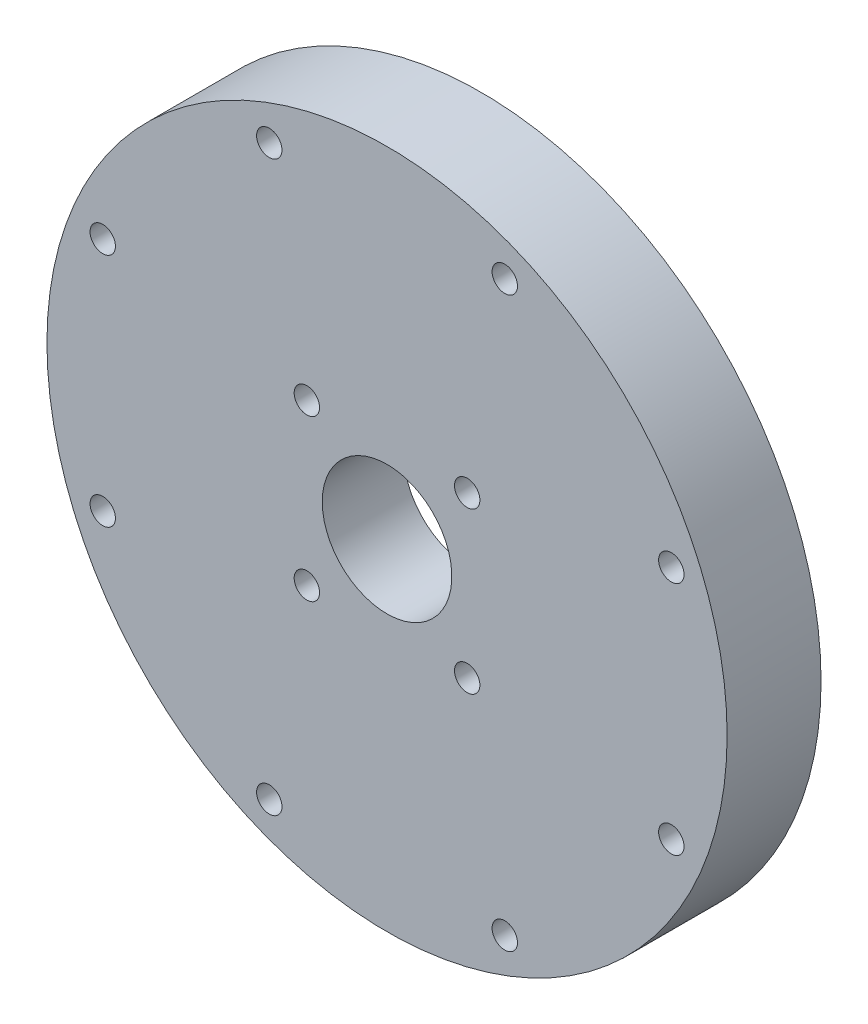
SolidWorks part; units mm, degrees
material "6061-T6 (SS)"
ref_plane "Front Plane" through (0, 0, 0) normal (0, 0, 1) x (1, 0, 0)
ref_plane "Top Plane" through (0, 0, 0) normal (0, 1, 0) x (1, 0, 0)
ref_plane "Right Plane" through (0, 0, 0) normal (1, 0, 0) x (0, 0, -1)
curve "Volute Curve"
  spline degree 3 poles (34.2618, 0, 0) (34.2648, 0.0718, 0) (34.2707, 0.2156, 0) (34.2778, 0.4312, 0) (34.2837, 0.647, 0) (34.2882, 0.8628, 0) (34.2914, 1.0787, 0) (34.2932, 1.2947, 0) (34.2937, 1.5108, 0) (34.2929, 1.7269, 0) (34.2907, 1.9431, 0) (34.2871, 2.1593, 0) (34.2822, 2.3756, 0) (34.2759, 2.5919, 0) (34.2683, 2.8082, 0) (34.2593, 3.0245, 0) (34.2489, 3.2407, 0) (34.2372, 3.457, 0) (34.2242, 3.6733, 0) (34.2098, 3.8895, 0) (34.194, 4.1058, 0) (34.1768, 4.3219, 0) (34.1583, 4.538, 0) (34.1385, 4.7541, 0) (34.1173, 4.9701, 0) (34.0947, 5.186, 0) (34.0708, 5.4018, 0) (34.0454, 5.6175, 0) (34.0188, 5.8331, 0) (33.9908, 6.0486, 0) (33.9614, 6.264, 0) (33.9306, 6.4793, 0) (33.8985, 6.6944, 0) (33.8651, 6.9094, 0) (33.8303, 7.1242, 0) (33.7941, 7.3388, 0) (33.7566, 7.5533, 0) (33.7177, 7.7676, 0) (33.6774, 7.9817, 0) (33.6358, 8.1956, 0) (33.5929, 8.4093, 0) (33.5486, 8.6228, 0) (33.5029, 8.8361, 0) (33.4559, 9.0491, 0) (33.4076, 9.2619, 0) (33.3579, 9.4745, 0) (33.3068, 9.6868, 0) (33.2544, 9.8988, 0) (33.2006, 10.1105, 0) (33.1456, 10.322, 0) (33.0891, 10.5332, 0) (33.0313, 10.744, 0) (32.9722, 10.9546, 0) (32.9118, 11.1648, 0) (32.85, 11.3748, 0) (32.7869, 11.5843, 0) (32.7224, 11.7936, 0) (32.6566, 12.0025, 0) (32.5895, 12.211, 0) (32.521, 12.4192, 0) (32.4513, 12.627, 0) (32.3802, 12.8344, 0) (32.3077, 13.0414, 0) (32.234, 13.248, 0) (32.1589, 13.4542, 0) (32.0826, 13.6599, 0) (32.0049, 13.8653, 0) (31.9259, 14.0702, 0) (31.8456, 14.2747, 0) (31.764, 14.4787, 0) (31.6811, 14.6823, 0) (31.5968, 14.8854, 0) (31.5113, 15.088, 0) (31.4245, 15.2901, 0) (31.3364, 15.4917, 0) (31.247, 15.6929, 0) (31.1563, 15.8935, 0) (31.0644, 16.0936, 0) (30.9711, 16.2932, 0) (30.8766, 16.4922, 0) (30.7808, 16.6907, 0) (30.6837, 16.8886, 0) (30.5854, 17.086, 0) (30.4858, 17.2829, 0) (30.3849, 17.4791, 0) (30.2828, 17.6748, 0) (30.1794, 17.8698, 0) (30.0747, 18.0643, 0) (29.9688, 18.2582, 0) (29.8617, 18.4514, 0) (29.7533, 18.644, 0) (29.6437, 18.836, 0) (29.5328, 19.0274, 0) (29.4208, 19.2181, 0) (29.3074, 19.4081, 0) (29.1929, 19.5975, 0) (29.0771, 19.7862, 0) (28.9601, 19.9742, 0) (28.842, 20.1616, 0) (28.7226, 20.3482, 0) (28.602, 20.5342, 0) (28.4801, 20.7194, 0) (28.3571, 20.904, 0) (28.233, 21.0877, 0) (28.1076, 21.2708, 0) (27.981, 21.4531, 0) (27.8533, 21.6347, 0) (27.7243, 21.8155, 0) (27.5942, 21.9956, 0) (27.463, 22.1748, 0) (27.3306, 22.3533, 0) (27.197, 22.531, 0) (27.0623, 22.708, 0) (26.9264, 22.8841, 0) (26.7894, 23.0594, 0) (26.6512, 23.2339, 0) (26.5119, 23.4075, 0) (26.3715, 23.5804, 0) (26.23, 23.7524, 0) (26.0873, 23.9235, 0) (25.9435, 24.0938, 0) (25.7987, 24.2632, 0) (25.6527, 24.4318, 0) (25.5056, 24.5995, 0) (25.3574, 24.7663, 0) (25.2082, 24.9322, 0) (25.0578, 25.0973, 0) (24.9064, 25.2614, 0) (24.7539, 25.4246, 0) (24.6003, 25.5869, 0) (24.4457, 25.7483, 0) (24.29, 25.9087, 0) (24.1333, 26.0682, 0) (23.9755, 26.2268, 0) (23.8167, 26.3844, 0) (23.6569, 26.541, 0) (23.496, 26.6967, 0) (23.3341, 26.8514, 0) (23.1712, 27.0051, 0) (23.0073, 27.1579, 0) (22.8424, 27.3096, 0) (22.6765, 27.4604, 0) (22.5096, 27.6101, 0) (22.3417, 27.7589, 0) (22.1728, 27.9066, 0) (22.003, 28.0533, 0) (21.8322, 28.199, 0) (21.6604, 28.3436, 0) (21.4877, 28.4872, 0) (21.314, 28.6297, 0) (21.1394, 28.7712, 0) (20.9639, 28.9116, 0) (20.7874, 29.051, 0) (20.61, 29.1892, 0) (20.4317, 29.3264, 0) (20.2524, 29.4626, 0) (20.0723, 29.5976, 0) (19.8913, 29.7315, 0) (19.7094, 29.8643, 0) (19.5266, 29.996, 0) (19.3429, 30.1266, 0) (19.1584, 30.2561, 0) (18.973, 30.3844, 0) (18.7867, 30.5116, 0) (18.5996, 30.6377, 0) (18.4117, 30.7626, 0) (18.2229, 30.8864, 0) (18.0333, 31.009, 0) (17.8429, 31.1304, 0) (17.6516, 31.2507, 0) (17.4596, 31.3698, 0) (17.2667, 31.4878, 0) (17.0731, 31.6045, 0) (16.8786, 31.7201, 0) (16.6834, 31.8344, 0) (16.4875, 31.9476, 0) (16.2907, 32.0596, 0) (16.0932, 32.1703, 0) (15.895, 32.2799, 0) (15.696, 32.3882, 0) (15.4963, 32.4953, 0) (15.2959, 32.6012, 0) (15.0947, 32.7058, 0) (14.8929, 32.8092, 0) (14.6903, 32.9114, 0) (14.487, 33.0123, 0) (14.2831, 33.1119, 0) (14.0784, 33.2103, 0) (13.8731, 33.3075, 0) (13.6672, 33.4033, 0) (13.4606, 33.4979, 0) (13.2533, 33.5912, 0) (13.0454, 33.6833, 0) (12.8368, 33.774, 0) (12.6277, 33.8635, 0) (12.4179, 33.9517, 0) (12.2075, 34.0385, 0) (11.9965, 34.1241, 0) (11.7849, 34.2084, 0) (11.5727, 34.2913, 0) (11.36, 34.373, 0) (11.1467, 34.4533, 0) (10.9328, 34.5323, 0) (10.7183, 34.61, 0) (10.5034, 34.6863, 0) (10.2879, 34.7613, 0) (10.0718, 34.835, 0) (9.8553, 34.9074, 0) (9.6382, 34.9783, 0) (9.4206, 35.048, 0) (9.2025, 35.1163, 0) (8.984, 35.1832, 0) (8.765, 35.2488, 0) (8.5455, 35.313, 0) (8.3255, 35.3759, 0) (8.1051, 35.4374, 0) (7.8842, 35.4975, 0) (7.6629, 35.5562, 0) (7.4412, 35.6136, 0) (7.2191, 35.6696, 0) (6.9965, 35.7242, 0) (6.7736, 35.7774, 0) (6.5503, 35.8292, 0) (6.3265, 35.8796, 0) (6.1024, 35.9287, 0) (5.878, 35.9763, 0) (5.6532, 36.0225, 0) (5.428, 36.0674, 0) (5.2025, 36.1108, 0) (4.9766, 36.1528, 0) (4.7505, 36.1934, 0) (4.524, 36.2326, 0) (4.2972, 36.2704, 0) (4.0701, 36.3067, 0) (3.8428, 36.3417, 0) (3.6151, 36.3752, 0) (3.3872, 36.4073, 0) (3.159, 36.438, 0) (2.9306, 36.4672, 0) (2.7019, 36.495, 0) (2.473, 36.5214, 0) (2.2439, 36.5463, 0) (2.0146, 36.5699, 0) (1.785, 36.5919, 0) (1.5553, 36.6126, 0) (1.3253, 36.6318, 0) (1.0952, 36.6495, 0) (0.8649, 36.6658, 0) (0.6345, 36.6807, 0) (0.4039, 36.6941, 0) (0.1731, 36.706, 0) (-0.0577, 36.7166, 0) (-0.2887, 36.7256, 0) (-0.5199, 36.7332, 0) (-0.7511, 36.7394, 0) (-0.9824, 36.7441, 0) (-1.2138, 36.7474, 0) (-1.4453, 36.7492, 0) (-1.6769, 36.7495, 0) (-1.9085, 36.7484, 0) (-2.1402, 36.7458, 0) (-2.3719, 36.7418, 0) (-2.6037, 36.7363, 0) (-2.8355, 36.7293, 0) (-3.0673, 36.7209, 0) (-3.2991, 36.711, 0) (-3.5309, 36.6997, 0) (-3.7627, 36.6869, 0) (-3.9944, 36.6726, 0) (-4.2262, 36.6569, 0) (-4.4579, 36.6397, 0) (-4.6895, 36.6211, 0) (-4.9211, 36.6009, 0) (-5.1526, 36.5794, 0) (-5.3841, 36.5563, 0) (-5.6154, 36.5318, 0) (-5.8467, 36.5059, 0) (-6.0779, 36.4784, 0) (-6.3089, 36.4495, 0) (-6.5399, 36.4192, 0) (-6.7706, 36.3874, 0) (-7.0013, 36.3541, 0) (-7.2318, 36.3194, 0) (-7.4621, 36.2832, 0) (-7.6923, 36.2455, 0) (-7.9223, 36.2064, 0) (-8.1521, 36.1658, 0) (-8.3817, 36.1238, 0) (-8.6111, 36.0803, 0) (-8.8403, 36.0354, 0) (-9.0693, 35.989, 0) (-9.298, 35.9411, 0) (-9.5265, 35.8918, 0) (-9.7548, 35.8411, 0) (-9.9827, 35.7889, 0) (-10.2105, 35.7352, 0) (-10.4379, 35.6802, 0) (-10.665, 35.6236, 0) (-10.8919, 35.5656, 0) (-11.1184, 35.5062, 0) (-11.3446, 35.4453, 0) (-11.5705, 35.383, 0) (-11.7961, 35.3193, 0) (-12.0213, 35.2541, 0) (-12.2461, 35.1875, 0) (-12.4706, 35.1194, 0) (-12.6948, 35.0499, 0) (-12.9185, 34.979, 0) (-13.1419, 34.9067, 0) (-13.3648, 34.8329, 0) (-13.5874, 34.7578, 0) (-13.8095, 34.6812, 0) (-14.0312, 34.6031, 0) (-14.2525, 34.5237, 0) (-14.4734, 34.4429, 0) (-14.6937, 34.3606, 0) (-14.9137, 34.2769, 0) (-15.1331, 34.1918, 0) (-15.3521, 34.1054, 0) (-15.5706, 34.0175, 0) (-15.7885, 33.9282, 0) (-16.006, 33.8375, 0) (-16.223, 33.7455, 0) (-16.4394, 33.652, 0) (-16.6553, 33.5572, 0) (-16.8707, 33.461, 0) (-17.0855, 33.3634, 0) (-17.2997, 33.2644, 0) (-17.5134, 33.164, 0) (-17.7265, 33.0623, 0) (-17.939, 32.9592, 0) (-18.151, 32.8548, 0) (-18.3623, 32.7489, 0) (-18.573, 32.6418, 0) (-18.7831, 32.5332, 0) (-18.9925, 32.4234, 0) (-19.2014, 32.3121, 0) (-19.4095, 32.1996, 0) (-19.6171, 32.0857, 0) (-19.8239, 31.9704, 0) (-20.0301, 31.8538, 0) (-20.2356, 31.7359, 0) (-20.4404, 31.6167, 0) (-20.6445, 31.4962, 0) (-20.8479, 31.3743, 0) (-21.0506, 31.2511, 0) (-21.2526, 31.1267, 0) (-21.4538, 31.0009, 0) (-21.6543, 30.8738, 0) (-21.854, 30.7454, 0) (-22.053, 30.6158, 0) (-22.2512, 30.4848, 0) (-22.4487, 30.3526, 0) (-22.6453, 30.2191, 0) (-22.8412, 30.0843, 0) (-23.0363, 29.9482, 0) (-23.2305, 29.8109, 0) (-23.424, 29.6723, 0) (-23.6166, 29.5325, 0) (-23.8084, 29.3915, 0) (-23.9994, 29.2491, 0) (-24.1895, 29.1056, 0) (-24.3787, 28.9608, 0) (-24.5671, 28.8148, 0) (-24.7546, 28.6676, 0) (-24.9413, 28.5191, 0) (-25.127, 28.3694, 0) (-25.3119, 28.2186, 0) (-25.4958, 28.0665, 0) (-25.6789, 27.9132, 0) (-25.861, 27.7587, 0) (-26.0422, 27.6031, 0) (-26.2224, 27.4463, 0) (-26.4018, 27.2882, 0) (-26.5801, 27.1291, 0) (-26.7576, 26.9687, 0) (-26.934, 26.8072, 0) (-27.1095, 26.6446, 0) (-27.284, 26.4808, 0) (-27.4575, 26.3159, 0) (-27.63, 26.1498, 0) (-27.8015, 25.9826, 0) (-27.972, 25.8143, 0) (-28.1415, 25.6448, 0) (-28.31, 25.4743, 0) (-28.4774, 25.3027, 0) (-28.6438, 25.1299, 0) (-28.8092, 24.9561, 0) (-28.9735, 24.7811, 0) (-29.1367, 24.6051, 0) (-29.2989, 24.4281, 0) (-29.46, 24.2499, 0) (-29.62, 24.0707, 0) (-29.7789, 23.8905, 0) (-29.9368, 23.7092, 0) (-30.0935, 23.5268, 0) (-30.2491, 23.3435, 0) (-30.4036, 23.1591, 0) (-30.557, 22.9737, 0) (-30.7093, 22.7872, 0) (-30.8604, 22.5998, 0) (-31.0104, 22.4114, 0) (-31.1592, 22.2219, 0) (-31.3069, 22.0315, 0) (-31.4534, 21.8402, 0) (-31.5988, 21.6478, 0) (-31.7429, 21.4545, 0) (-31.8859, 21.2602, 0) (-32.0277, 21.065, 0) (-32.1684, 20.8688, 0) (-32.3078, 20.6717, 0) (-32.446, 20.4737, 0) (-32.583, 20.2747, 0) (-32.7188, 20.0748, 0) (-32.8533, 19.8741, 0) (-32.9866, 19.6724, 0) (-33.1187, 19.4698, 0) (-33.2496, 19.2664, 0) (-33.3792, 19.0621, 0) (-33.5075, 18.8569, 0) (-33.6346, 18.6509, 0) (-33.7604, 18.444, 0) (-33.885, 18.2362, 0) (-34.0082, 18.0276, 0) (-34.1302, 17.8182, 0) (-34.2509, 17.608, 0) (-34.3703, 17.397, 0) (-34.4884, 17.1851, 0) (-34.6052, 16.9725, 0) (-34.7207, 16.7591, 0) (-34.8349, 16.5449, 0) (-34.9478, 16.3299, 0) (-35.0593, 16.1141, 0) (-35.1695, 15.8976, 0) (-35.2784, 15.6804, 0) (-35.3859, 15.4624, 0) (-35.4921, 15.2436, 0) (-35.597, 15.0242, 0) (-35.7004, 14.804, 0) (-35.8026, 14.5832, 0) (-35.9033, 14.3616, 0) (-36.0027, 14.1393, 0) (-36.1007, 13.9164, 0) (-36.1973, 13.6928, 0) (-36.2926, 13.4685, 0) (-36.3864, 13.2436, 0) (-36.4789, 13.018, 0) (-36.57, 12.7918, 0) (-36.6596, 12.5649, 0) (-36.7479, 12.3374, 0) (-36.8348, 12.1094, 0) (-36.9202, 11.8807, 0) (-37.0042, 11.6514, 0) (-37.0868, 11.4215, 0) (-37.168, 11.1911, 0) (-37.2477, 10.96, 0) (-37.326, 10.7285, 0) (-37.4029, 10.4963, 0) (-37.4783, 10.2637, 0) (-37.5523, 10.0305, 0) (-37.6248, 9.7967, 0) (-37.6959, 9.5625, 0) (-37.7655, 9.3277, 0) (-37.8337, 9.0925, 0) (-37.9004, 8.8568, 0) (-37.9656, 8.6205, 0) (-38.0293, 8.3839, 0) (-38.0916, 8.1467, 0) (-38.1524, 7.9091, 0) (-38.2117, 7.6711, 0) (-38.2696, 7.4326, 0) (-38.3259, 7.1937, 0) (-38.3808, 6.9544, 0) (-38.4342, 6.7147, 0) (-38.486, 6.4746, 0) (-38.5364, 6.2341, 0) (-38.5853, 5.9932, 0) (-38.6326, 5.7519, 0) (-38.6785, 5.5103, 0) (-38.7229, 5.2684, 0) (-38.7657, 5.0261, 0) (-38.807, 4.7835, 0) (-38.8468, 4.5405, 0) (-38.8851, 4.2973, 0) (-38.9219, 4.0537, 0) (-38.9571, 3.8099, 0) (-38.9908, 3.5657, 0) (-39.023, 3.3213, 0) (-39.0537, 3.0767, 0) (-39.0828, 2.8317, 0) (-39.1104, 2.5866, 0) (-39.1364, 2.3412, 0) (-39.1609, 2.0955, 0) (-39.1839, 1.8497, 0) (-39.2053, 1.6037, 0) (-39.2252, 1.3574, 0) (-39.2435, 1.111, 0) (-39.2603, 0.8644, 0) (-39.2756, 0.6176, 0) (-39.2893, 0.3707, 0) (-39.3014, 0.1236, 0) (-39.312, -0.1236, 0) (-39.321, -0.371, 0) (-39.3285, -0.6185, 0) (-39.3344, -0.866, 0) (-39.3388, -1.1137, 0) (-39.3416, -1.3615, 0) (-39.3428, -1.6093, 0) (-39.3425, -1.8572, 0) (-39.3406, -2.1052, 0) (-39.3372, -2.3532, 0) (-39.3322, -2.6013, 0) (-39.3257, -2.8494, 0) (-39.3175, -3.0975, 0) (-39.3078, -3.3456, 0) (-39.2966, -3.5937, 0) (-39.2838, -3.8418, 0) (-39.2694, -4.0899, 0) (-39.2534, -4.338, 0) (-39.2359, -4.586, 0) (-39.2168, -4.834, 0) (-39.1962, -5.0819, 0) (-39.174, -5.3298, 0) (-39.1502, -5.5776, 0) (-39.1248, -5.8252, 0) (-39.0979, -6.0728, 0) (-39.0694, -6.3203, 0) (-39.0394, -6.5677, 0) (-39.0078, -6.8149, 0) (-38.9746, -7.062, 0) (-38.9399, -7.309, 0) (-38.9036, -7.5558, 0) (-38.8657, -7.8024, 0) (-38.8263, -8.0488, 0) (-38.7853, -8.2951, 0) (-38.7427, -8.5411, 0) (-38.6986, -8.787, 0) (-38.653, -9.0326, 0) (-38.6057, -9.2781, 0) (-38.557, -9.5232, 0) (-38.5066, -9.7682, 0) (-38.4547, -10.0128, 0) (-38.4013, -10.2572, 0) (-38.3463, -10.5014, 0) (-38.2897, -10.7452, 0) (-38.2316, -10.9888, 0) (-38.172, -11.232, 0) (-38.1108, -11.475, 0) (-38.048, -11.7176, 0) (-37.9838, -11.9598, 0) (-37.9179, -12.2018, 0) (-37.8506, -12.4433, 0) (-37.7817, -12.6845, 0) (-37.7112, -12.9254, 0) (-37.6393, -13.1658, 0) (-37.5658, -13.4059, 0) (-37.4907, -13.6455, 0) (-37.4142, -13.8848, 0) (-37.3361, -14.1236, 0) (-37.2565, -14.362, 0) (-37.1753, -14.5999, 0) (-37.0927, -14.8374, 0) (-37.0085, -15.0744, 0) (-36.9228, -15.311, 0) (-36.8357, -15.547, 0) (-36.747, -15.7826, 0) (-36.6568, -16.0177, 0) (-36.5651, -16.2523, 0) (-36.4719, -16.4863, 0) (-36.3772, -16.7199, 0) (-36.281, -16.9528, 0) (-36.1833, -17.1853, 0) (-36.0841, -17.4172, 0) (-35.9834, -17.6485, 0) (-35.8813, -17.8792, 0) (-35.7777, -18.1094, 0) (-35.6726, -18.3389, 0) (-35.566, -18.5679, 0) (-35.458, -18.7962, 0) (-35.3485, -19.0239, 0) (-35.2376, -19.251, 0) (-35.1251, -19.4774, 0) (-35.0113, -19.7032, 0) (-34.896, -19.9283, 0) (-34.7792, -20.1528, 0) (-34.661, -20.3765, 0) (-34.5414, -20.5996, 0) (-34.4203, -20.822, 0) (-34.2978, -21.0437, 0) (-34.1738, -21.2646, 0) (-34.0485, -21.4849, 0) (-33.9217, -21.7044, 0) (-33.7935, -21.9231, 0) (-33.6639, -22.1411, 0) (-33.5329, -22.3584, 0) (-33.4005, -22.5748, 0) (-33.2667, -22.7905, 0) (-33.1315, -23.0054, 0) (-32.995, -23.2195, 0) (-32.857, -23.4328, 0) (-32.7177, -23.6453, 0) (-32.577, -23.8569, 0) (-32.4349, -24.0677, 0) (-32.2915, -24.2777, 0) (-32.1467, -24.4868, 0) (-32.0006, -24.6951, 0) (-31.8531, -24.9025, 0) (-31.7042, -25.109, 0) (-31.5541, -25.3146, 0) (-31.4026, -25.5194, 0) (-31.2497, -25.7232, 0) (-31.0956, -25.9261, 0) (-30.9401, -26.1281, 0) (-30.7833, -26.3292, 0) (-30.6253, -26.5293, 0) (-30.4659, -26.7285, 0) (-30.3052, -26.9267, 0) (-30.1433, -27.124, 0) (-29.98, -27.3203, 0) (-29.8155, -27.5156, 0) (-29.6497, -27.7099, 0) (-29.4827, -27.9032, 0) (-29.3144, -28.0956, 0) (-29.1448, -28.2869, 0) (-28.974, -28.4772, 0) (-28.8019, -28.6664, 0) (-28.6287, -28.8546, 0) (-28.4542, -29.0418, 0) (-28.2784, -29.2279, 0) (-28.1015, -29.413, 0) (-27.9233, -29.597, 0) (-27.744, -29.7799, 0) (-27.5634, -29.9618, 0) (-27.3817, -30.1425, 0) (-27.1987, -30.3221, 0) (-27.0146, -30.5007, 0) (-26.8294, -30.6781, 0) (-26.6429, -30.8544, 0) (-26.4554, -31.0296, 0) (-26.2666, -31.2036, 0) (-26.0767, -31.3765, 0) (-25.8857, -31.5482, 0) (-25.6936, -31.7188, 0) (-25.5003, -31.8882, 0) (-25.306, -32.0564, 0) (-25.1105, -32.2234, 0) (-24.9139, -32.3893, 0) (-24.7162, -32.5539, 0) (-24.5175, -32.7174, 0) (-24.3176, -32.8796, 0) (-24.1167, -33.0406, 0) (-23.9147, -33.2004, 0) (-23.7117, -33.359, 0) (-23.5076, -33.5163, 0) (-23.3025, -33.6724, 0) (-23.0964, -33.8272, 0) (-22.8892, -33.9807, 0) (-22.681, -34.133, 0) (-22.4718, -34.2841, 0) (-22.2616, -34.4338, 0) (-22.0504, -34.5822, 0) (-21.8382, -34.7294, 0) (-21.6251, -34.8752, 0) (-21.4109, -35.0198, 0) (-21.1959, -35.163, 0) (-20.9798, -35.3049, 0) (-20.7628, -35.4455, 0) (-20.5449, -35.5848, 0) (-20.326, -35.7227, 0) (-20.1062, -35.8593, 0) (-19.8855, -35.9945, 0) (-19.6639, -36.1284, 0) (-19.4414, -36.2609, 0) (-19.2181, -36.392, 0) (-18.9938, -36.5218, 0) (-18.7686, -36.6502, 0) (-18.5426, -36.7772, 0) (-18.3158, -36.9028, 0) (-18.0881, -37.027, 0) (-17.8595, -37.1498, 0) (-17.6302, -37.2712, 0) (-17.4, -37.3911, 0) (-17.169, -37.5097, 0) (-16.9372, -37.6268, 0) (-16.7046, -37.7425, 0) (-16.4712, -37.8568, 0) (-16.237, -37.9696, 0) (-16.0021, -38.081, 0) (-15.7664, -38.1909, 0) (-15.53, -38.2994, 0) (-15.2928, -38.4064, 0) (-15.0549, -38.5119, 0) (-14.8163, -38.616, 0) (-14.577, -38.7185, 0) (-14.3369, -38.8196, 0) (-14.0962, -38.9192, 0) (-13.8547, -39.0174, 0) (-13.6126, -39.114, 0) (-13.3699, -39.2091, 0) (-13.1265, -39.3027, 0) (-12.8824, -39.3949, 0) (-12.6377, -39.4854, 0) (-12.3923, -39.5745, 0) (-12.1464, -39.6621, 0) (-11.8998, -39.7481, 0) (-11.6526, -39.8326, 0) (-11.4048, -39.9155, 0) (-11.1565, -39.997, 0) (-10.9076, -40.0768, 0) (-10.6581, -40.1552, 0) (-10.408, -40.2319, 0) (-10.1575, -40.3071, 0) (-9.9063, -40.3808, 0) (-9.6547, -40.4529, 0) (-9.4025, -40.5234, 0) (-9.1499, -40.5924, 0) (-8.8967, -40.6598, 0) (-8.6431, -40.7256, 0) (-8.389, -40.7898, 0) (-8.1344, -40.8524, 0) (-7.8793, -40.9135, 0) (-7.6239, -40.9729, 0) (-7.3679, -41.0308, 0) (-7.1116, -41.087, 0) (-6.8548, -41.1417, 0) (-6.5977, -41.1948, 0) (-6.3401, -41.2462, 0) (-6.0821, -41.2961, 0) (-5.8238, -41.3443, 0) (-5.5651, -41.3909, 0) (-5.3061, -41.4359, 0) (-5.0467, -41.4793, 0) (-4.7869, -41.5211, 0) (-4.5269, -41.5612, 0) (-4.2665, -41.5997, 0) (-4.0058, -41.6366, 0) (-3.7449, -41.6718, 0) (-3.4836, -41.7054, 0) (-3.2221, -41.7374, 0) (-2.9603, -41.7677, 0) (-2.6982, -41.7964, 0) (-2.4359, -41.8234, 0) (-2.1734, -41.8488, 0) (-1.9106, -41.8726, 0) (-1.6477, -41.8947, 0) (-1.3845, -41.9151, 0) (-1.1212, -41.9339, 0) (-0.8576, -41.9511, 0) (-0.5939, -41.9666, 0) (-0.33, -41.9804, 0) (-0.066, -41.9926, 0) (0.1981, -42.0031, 0) (0.4624, -42.012, 0) (0.7268, -42.0192, 0) (0.9914, -42.0247, 0) (1.256, -42.0286, 0) (1.5207, -42.0308, 0) (1.7855, -42.0313, 0) (2.0503, -42.0302, 0) (2.3152, -42.0274, 0) (2.5802, -42.0229, 0) (2.8452, -42.0168, 0) (3.1102, -42.0089, 0) (3.3752, -41.9995, 0) (3.6403, -41.9883, 0) (3.9053, -41.9755, 0) (4.1703, -41.961, 0) (4.4353, -41.9448, 0) (4.7002, -41.927, 0) (4.9651, -41.9075, 0) (5.2299, -41.8863, 0) (5.4947, -41.8634, 0) (5.7594, -41.8389, 0) (6.024, -41.8127, 0) (6.2885, -41.7848, 0) (6.5528, -41.7553, 0) (6.8171, -41.7241, 0) (7.0812, -41.6912, 0) (7.3452, -41.6566, 0) (7.609, -41.6204, 0) (7.8727, -41.5825, 0) (8.1362, -41.5429, 0) (8.3995, -41.5017, 0) (8.6626, -41.4588, 0) (8.9254, -41.4142, 0) (9.1881, -41.3679, 0) (9.4506, -41.32, 0) (9.7128, -41.2705, 0) (9.9747, -41.2192, 0) (10.2364, -41.1663, 0) (10.4979, -41.1118, 0) (10.759, -41.0556, 0) (11.0199, -40.9977, 0) (11.2804, -40.9382, 0) (11.5407, -40.877, 0) (11.8006, -40.8141, 0) (12.0602, -40.7496, 0) (12.3194, -40.6835, 0) (12.5783, -40.6157, 0) (12.8368, -40.5463, 0) (13.0949, -40.4752, 0) (13.3527, -40.4025, 0) (13.6101, -40.3281, 0) (13.867, -40.2521, 0) (14.1235, -40.1745, 0) (14.3797, -40.0952, 0) (14.6353, -40.0143, 0) (14.8905, -39.9318, 0) (15.1453, -39.8476, 0) (15.3996, -39.7618, 0) (15.6534, -39.6744, 0) (15.9067, -39.5854, 0) (16.1596, -39.4948, 0) (16.4119, -39.4025, 0) (16.6637, -39.3087, 0) (16.9149, -39.2132, 0) (17.1657, -39.1161, 0) (17.4158, -39.0174, 0) (17.6654, -38.9172, 0) (17.9145, -38.8153, 0) (18.1629, -38.7118, 0) (18.4108, -38.6068, 0) (18.658, -38.5001, 0) (18.9047, -38.3919, 0) (19.1507, -38.2821, 0) (19.3961, -38.1707, 0) (19.6408, -38.0578, 0) (19.8849, -37.9433, 0) (20.1283, -37.8272, 0) (20.3711, -37.7095, 0) (20.6132, -37.5904, 0) (20.8546, -37.4696, 0) (21.0952, -37.3473, 0) (21.3352, -37.2235, 0) (21.5744, -37.0981, 0) (21.8129, -36.9712, 0) (22.0507, -36.8427, 0) (22.2877, -36.7127, 0) (22.524, -36.5812, 0) (22.7594, -36.4482, 0) (22.9941, -36.3137, 0) (23.228, -36.1776, 0) (23.4611, -36.0401, 0) (23.6934, -35.901, 0) (23.9249, -35.7605, 0) (24.1556, -35.6184, 0) (24.3854, -35.4749, 0) (24.6143, -35.3299, 0) (24.8424, -35.1834, 0) (25.0696, -35.0355, 0) (25.296, -34.8861, 0) (25.5214, -34.7352, 0) (25.746, -34.5828, 0) (25.9696, -34.4291, 0) (26.1924, -34.2738, 0) (26.4142, -34.1172, 0) (26.6351, -33.9591, 0) (26.855, -33.7995, 0) (27.074, -33.6386, 0) (27.292, -33.4762, 0) (27.5091, -33.3124, 0) (27.7252, -33.1472, 0) (27.9402, -32.9807, 0) (28.1543, -32.8127, 0) (28.3674, -32.6433, 0) (28.5795, -32.4726, 0) (28.7905, -32.3004, 0) (29.0005, -32.127, 0) (29.2095, -31.9521, 0) (29.4174, -31.7759, 0) (29.6242, -31.5983, 0) (29.83, -31.4194, 0) (30.0347, -31.2392, 0) (30.2383, -31.0576, 0) (30.4408, -30.8747, 0) (30.6422, -30.6905, 0) (30.8426, -30.5049, 0) (31.0417, -30.3181, 0) (31.2398, -30.1299, 0) (31.4367, -29.9405, 0) (31.6325, -29.7498, 0) (31.8271, -29.5578, 0) (32.0205, -29.3645, 0) (32.2128, -29.17, 0) (32.4039, -28.9742, 0) (32.5938, -28.7772, 0) (32.7825, -28.5789, 0) (32.97, -28.3794, 0) (33.1563, -28.1787, 0) (33.3414, -27.9767, 0) (33.5252, -27.7736, 0) (33.7079, -27.5692, 0) (33.8892, -27.3636, 0) (34.0693, -27.1569, 0) (34.2482, -26.9489, 0) (34.4258, -26.7398, 0) (34.6021, -26.5295, 0) (34.7771, -26.3181, 0) (34.9509, -26.1055, 0) (35.1233, -25.8917, 0) (35.2944, -25.6768, 0) (35.4643, -25.4608, 0) (35.6328, -25.2437, 0) (35.7999, -25.0255, 0) (35.9658, -24.8061, 0) (36.1303, -24.5857, 0) (36.2934, -24.3641, 0) (36.4552, -24.1415, 0) (36.6157, -23.9179, 0) (36.7747, -23.6931, 0) (36.9324, -23.4673, 0) (37.0887, -23.2405, 0) (37.2436, -23.0126, 0) (37.3971, -22.7837, 0) (37.5492, -22.5538, 0) (37.6999, -22.3228, 0) (37.8491, -22.0909, 0) (37.997, -21.858, 0) (38.1434, -21.624, 0) (38.2884, -21.3891, 0) (38.4319, -21.1533, 0) (38.574, -20.9165, 0) (38.7146, -20.6787, 0) (38.8537, -20.44, 0) (38.9914, -20.2003, 0) (39.1276, -19.9598, 0) (39.2623, -19.7183, 0) (39.3956, -19.4759, 0) (39.5273, -19.2326, 0) (39.6575, -18.9884, 0) (39.7863, -18.7434, 0) (39.9135, -18.4975, 0) (40.0392, -18.2507, 0) (40.1633, -18.0031, 0) (40.286, -17.7546, 0) (40.4071, -17.5053, 0) (40.5267, -17.2552, 0) (40.6447, -17.0043, 0) (40.7611, -16.7525, 0) (40.876, -16.5, 0) (40.9894, -16.2467, 0) (41.1012, -15.9927, 0) (41.2114, -15.7378, 0) (41.32, -15.4822, 0) (41.427, -15.2259, 0) (41.5325, -14.9688, 0) (41.6363, -14.711, 0) (41.7386, -14.4525, 0) (41.8392, -14.1933, 0) (41.9383, -13.9334, 0) (42.0357, -13.6728, 0) (42.1315, -13.4116, 0) (42.2257, -13.1496, 0) (42.3182, -12.8871, 0) (42.4092, -12.6238, 0) (42.4985, -12.36, 0) (42.5861, -12.0955, 0) (42.6721, -11.8304, 0) (42.7565, -11.5647, 0) (42.8392, -11.2984, 0) (42.9202, -11.0315, 0) (42.9996, -10.7641, 0) (43.0773, -10.4961, 0) (43.1534, -10.2275, 0) (43.2277, -9.9584, 0) (43.3004, -9.6888, 0) (43.3715, -9.4186, 0) (43.4408, -9.148, 0) (43.5084, -8.8768, 0) (43.5744, -8.6052, 0) (43.6386, -8.333, 0) (43.7012, -8.0604, 0) (43.7621, -7.7874, 0) (43.8212, -7.5139, 0) (43.8786, -7.24, 0) (43.9344, -6.9656, 0) (43.9884, -6.6908, 0) (44.0407, -6.4156, 0) (44.0913, -6.1401, 0) (44.1401, -5.8641, 0) (44.1872, -5.5878, 0) (44.2326, -5.3111, 0) (44.2763, -5.0341, 0) (44.3182, -4.7567, 0) (44.3584, -4.479, 0) (44.3969, -4.201, 0) (44.4336, -3.9226, 0) (44.4686, -3.644, 0) (44.5018, -3.3651, 0) (44.5333, -3.0859, 0) (44.563, -2.8065, 0) (44.591, -2.5268, 0) (44.6172, -2.2468, 0) (44.6416, -1.9667, 0) (44.6643, -1.6863, 0) (44.6853, -1.4057, 0) (44.7044, -1.1249, 0) (44.7219, -0.8439, 0) (44.7375, -0.5628, 0) (44.7515, -0.2815, 0) (44.7593, -0.0938, 0) (44.7632, 0, 0) knots 0 0 0 0 0.000871 0.001743 0.002614 0.003486 0.004358 0.005231 0.006103 0.006976 0.007849 0.008723 0.009596 0.01047 0.011344 0.012219 0.013093 0.013968 0.014843 0.015718 0.016594 0.017469 0.018345 0.019222 0.020098 0.020975 0.021852 0.022729 0.023606 0.024484 0.025362 0.02624 0.027119 0.027997 0.028876 0.029755 0.030635 0.031514 0.032394 0.033274 0.034154 0.035035 0.035916 0.036797 0.037678 0.03856 0.039442 0.040324 0.041206 0.042089 0.042971 0.043854 0.044738 0.045621 0.046505 0.047389 0.048273 0.049158 0.050042 0.050927 0.051813 0.052698 0.053584 0.05447 0.055356 0.056242 0.057129 0.058016 0.058903 0.059791 0.060678 0.061566 0.062454 0.063343 0.064232 0.06512 0.06601 0.066899 0.067789 0.068679 0.069569 0.070459 0.07135 0.072241 0.073132 0.074023 0.074915 0.075807 0.076699 0.077591 0.078484 0.079377 0.08027 0.081163 0.082057 0.082951 0.083845 0.084739 0.085634 0.086529 0.087424 0.088319 0.089215 0.090111 0.091007 0.091903 0.0928 0.093696 0.094594 0.095491 0.096388 0.097286 0.098184 0.099083 0.099981 0.10088 0.101779 0.102679 0.103578 0.104478 0.105378 0.106279 0.107179 0.10808 0.108981 0.109882 0.110784 0.111686 0.112588 0.11349 0.114393 0.115296 0.116199 0.117102 0.118006 0.11891 0.119814 0.120718 0.121623 0.122528 0.123433 0.124338 0.125244 0.12615 0.127056 0.127962 0.128869 0.129776 0.130683 0.13159 0.132498 0.133406 0.134314 0.135222 0.136131 0.13704 0.137949 0.138858 0.139768 0.140678 0.141588 0.142498 0.143409 0.14432 0.145231 0.146142 0.147054 0.147966 0.148878 0.149791 0.150703 0.151616 0.152529 0.153443 0.154357 0.155271 0.156185 0.157099 0.158014 0.158929 0.159844 0.16076 0.161675 0.162591 0.163508 0.164424 0.165341 0.166258 0.167175 0.168093 0.16901 0.169928 0.170847 0.171765 0.172684 0.173603 0.174522 0.175442 0.176362 0.177282 0.178202 0.179123 0.180044 0.180965 0.181886 0.182808 0.183729 0.184652 0.185574 0.186497 0.187419 0.188343 0.189266 0.19019 0.191113 0.192038 0.192962 0.193887 0.194812 0.195737 0.196662 0.197588 0.198514 0.19944 0.200367 0.201293 0.20222 0.203147 0.204075 0.205003 0.205931 0.206859 0.207787 0.208716 0.209645 0.210575 0.211504 0.212434 0.213364 0.214294 0.215225 0.216156 0.217087 0.218018 0.21895 0.219882 0.220814 0.221746 0.222679 0.223612 0.224545 0.225478 0.226412 0.227346 0.22828 0.229214 0.230149 0.231084 0.232019 0.232955 0.23389 0.234826 0.235763 0.236699 0.237636 0.238573 0.23951 0.240448 0.241386 0.242324 0.243262 0.244201 0.245139 0.246078 0.247018 0.247957 0.248897 0.249837 0.250778 0.251718 0.252659 0.253601 0.254542 0.255484 0.256426 0.257368 0.25831 0.259253 0.260196 0.261139 0.262083 0.263027 0.263971 0.264915 0.265859 0.266804 0.267749 0.268695 0.26964 0.270586 0.271532 0.272479 0.273425 0.274372 0.275319 0.276267 0.277214 0.278162 0.27911 0.280059 0.281008 0.281957 0.282906 0.283855 0.284805 0.285755 0.286705 0.287656 0.288607 0.289558 0.290509 0.291461 0.292413 0.293365 0.294317 0.29527 0.296223 0.297176 0.298129 0.299083 0.300037 0.300991 0.301946 0.3029 0.303855 0.30481 0.305766 0.306722 0.307678 0.308634 0.309591 0.310548 0.311505 0.312462 0.31342 0.314377 0.315336 0.316294 0.317253 0.318212 0.319171 0.32013 0.32109 0.32205 0.32301 0.323971 0.324931 0.325892 0.326854 0.327815 0.328777 0.329739 0.330702 0.331664 0.332627 0.33359 0.334554 0.335517 0.336481 0.337445 0.33841 0.339375 0.34034 0.341305 0.34227 0.343236 0.344202 0.345168 0.346135 0.347102 0.348069 0.349036 0.350004 0.350972 0.35194 0.352908 0.353877 0.354846 0.355815 0.356785 0.357754 0.358724 0.359695 0.360665 0.361636 0.362607 0.363578 0.36455 0.365522 0.366494 0.367466 0.368439 0.369412 0.370385 0.371358 0.372332 0.373306 0.37428 0.375255 0.37623 0.377205 0.37818 0.379156 0.380131 0.381107 0.382084 0.38306 0.384037 0.385015 0.385992 0.38697 0.387948 0.388926 0.389904 0.390883 0.391862 0.392841 0.393821 0.394801 0.395781 0.396761 0.397742 0.398723 0.399704 0.400685 0.401667 0.402649 0.403631 0.404614 0.405596 0.406579 0.407563 0.408546 0.40953 0.410514 0.411498 0.412483 0.413468 0.414453 0.415438 0.416424 0.41741 0.418396 0.419383 0.420369 0.421357 0.422344 0.423331 0.424319 0.425307 0.426296 0.427284 0.428273 0.429262 0.430252 0.431241 0.432231 0.433222 0.434212 0.435203 0.436194 0.437185 0.438177 0.439169 0.440161 0.441153 0.442146 0.443139 0.444132 0.445125 0.446119 0.447113 0.448107 0.449102 0.450096 0.451091 0.452087 0.453082 0.454078 0.455074 0.456071 0.457067 0.458064 0.459061 0.460059 0.461057 0.462055 0.463053 0.464051 0.46505 0.466049 0.467049 0.468048 0.469048 0.470048 0.471049 0.472049 0.47305 0.474052 0.475053 0.476055 0.477057 0.478059 0.479062 0.480065 0.481068 0.482071 0.483075 0.484079 0.485083 0.486087 0.487092 0.488097 0.489102 0.490108 0.491114 0.49212 0.493126 0.494133 0.49514 0.496147 0.497154 0.498162 0.49917 0.500178 0.501187 0.502196 0.503205 0.504214 0.505224 0.506233 0.507244 0.508254 0.509265 0.510276 0.511287 0.512298 0.51331 0.514322 0.515334 0.516347 0.51736 0.518373 0.519386 0.5204 0.521414 0.522428 0.523442 0.524457 0.525472 0.526488 0.527503 0.528519 0.529535 0.530551 0.531568 0.532585 0.533602 0.53462 0.535637 0.536655 0.537673 0.538692 0.539711 0.54073 0.541749 0.542769 0.543789 0.544809 0.545829 0.54685 0.547871 0.548892 0.549914 0.550936 0.551958 0.55298 0.554003 0.555026 0.556049 0.557072 0.558096 0.55912 0.560144 0.561169 0.562193 0.563218 0.564244 0.565269 0.566295 0.567321 0.568348 0.569375 0.570402 0.571429 0.572456 0.573484 0.574512 0.575541 0.576569 0.577598 0.578627 0.579657 0.580686 0.581716 0.582747 0.583777 0.584808 0.585839 0.58687 0.587902 0.588934 0.589966 0.590998 0.592031 0.593064 0.594097 0.595131 0.596165 0.597199 0.598233 0.599268 0.600303 0.601338 0.602373 0.603409 0.604445 0.605481 0.606518 0.607554 0.608592 0.609629 0.610667 0.611704 0.612743 0.613781 0.61482 0.615859 0.616898 0.617938 0.618977 0.620018 0.621058 0.622099 0.62314 0.624181 0.625222 0.626264 0.627306 0.628348 0.629391 0.630434 0.631477 0.63252 0.633564 0.634608 0.635652 0.636697 0.637741 0.638786 0.639832 0.640877 0.641923 0.642969 0.644016 0.645062 0.646109 0.647157 0.648204 0.649252 0.6503 0.651348 0.652397 0.653446 0.654495 0.655545 0.656594 0.657644 0.658695 0.659745 0.660796 0.661847 0.662898 0.66395 0.665002 0.666054 0.667107 0.668159 0.669212 0.670266 0.671319 0.672373 0.673427 0.674482 0.675536 0.676591 0.677647 0.678702 0.679758 0.680814 0.68187 0.682927 0.683984 0.685041 0.686099 0.687156 0.688214 0.689273 0.690331 0.69139 0.692449 0.693508 0.694568 0.695628 0.696688 0.697749 0.69881 0.699871 0.700932 0.701994 0.703055 0.704118 0.70518 0.706243 0.707306 0.708369 0.709433 0.710496 0.71156 0.712625 0.713689 0.714754 0.71582 0.716885 0.717951 0.719017 0.720083 0.72115 0.722217 0.723284 0.724351 0.725419 0.726487 0.727555 0.728624 0.729693 0.730762 0.731831 0.732901 0.733971 0.735041 0.736111 0.737182 0.738253 0.739324 0.740396 0.741468 0.74254 0.743612 0.744685 0.745758 0.746831 0.747905 0.748979 0.750053 0.751127 0.752202 0.753277 0.754352 0.755428 0.756503 0.757579 0.758656 0.759732 0.760809 0.761886 0.762964 0.764041 0.765119 0.766198 0.767276 0.768355 0.769434 0.770514 0.771593 0.772673 0.773754 0.774834 0.775915 0.776996 0.778077 0.779159 0.780241 0.781323 0.782405 0.783488 0.784571 0.785654 0.786738 0.787822 0.788906 0.789991 0.791075 0.79216 0.793245 0.794331 0.795417 0.796503 0.797589 0.798676 0.799763 0.80085 0.801938 0.803025 0.804113 0.805202 0.80629 0.807379 0.808468 0.809558 0.810648 0.811738 0.812828 0.813919 0.815009 0.816101 0.817192 0.818284 0.819376 0.820468 0.82156 0.822653 0.823746 0.82484 0.825933 0.827027 0.828122 0.829216 0.830311 0.831406 0.832501 0.833597 0.834693 0.835789 0.836885 0.837982 0.839079 0.840177 0.841274 0.842372 0.84347 0.844569 0.845667 0.846766 0.847866 0.848965 0.850065 0.851165 0.852266 0.853366 0.854467 0.855568 0.85667 0.857772 0.858874 0.859976 0.861079 0.862182 0.863285 0.864389 0.865492 0.866596 0.867701 0.868805 0.86991 0.871016 0.872121 0.873227 0.874333 0.875439 0.876546 0.877653 0.87876 0.879867 0.880975 0.882083 0.883191 0.8843 0.885409 0.886518 0.887627 0.888737 0.889847 0.890957 0.892068 0.893179 0.89429 0.895401 0.896513 0.897625 0.898737 0.89985 0.900962 0.902075 0.903189 0.904303 0.905416 0.906531 0.907645 0.90876 0.909875 0.91099 0.912106 0.913222 0.914338 0.915455 0.916571 0.917689 0.918806 0.919923 0.921041 0.92216 0.923278 0.924397 0.925516 0.926635 0.927755 0.928875 0.929995 0.931115 0.932236 0.933357 0.934478 0.9356 0.936722 0.937844 0.938966 0.940089 0.941212 0.942335 0.943459 0.944583 0.945707 0.946831 0.947956 0.949081 0.950206 0.951332 0.952458 0.953584 0.95471 0.955837 0.956964 0.958091 0.959219 0.960347 0.961475 0.962603 0.963732 0.964861 0.96599 0.96712 0.968249 0.96938 0.97051 0.971641 0.972772 0.973903 0.975034 0.976166 0.977298 0.978431 0.979563 0.980696 0.981829 0.982963 0.984097 0.985231 0.986365 0.9875 0.988635 0.98977 0.990906 0.992041 0.993178 0.994314 0.995451 0.996587 0.997725 0.998862 1 1 1 1
sketch "Sketch16" plane through (0, 0, 0) normal (0, 1, 0) x (1, 0, 0)
  line L0 (12.7, -24.13) -> (66.675, -24.13)
  line L1 (66.675, -24.13) -> (66.675, 0)
  line L2 (66.675, 0) -> (12.7, 0)
  line L3 (12.7, 0) -> (12.7, -24.13)
  line L8 (0, 0) -> (0, -24.13) construction
  dimension "D1" = 133.35
  dimension "D3" = 24.13
  dimension "D7" = 25.4
revolve "Main Body" add sketch "Sketch16" angle 360 about L8
sketch "Sketch18" plane through (0, 0, 0) normal (0, 0, -1) x (-1, 0, 0)
  arc A13 (-43.8192, -7.5219) -> (-38.9898, 0) centre (-37.6087, -6.198) cw construction
  arc A14 (-34.0631, 5.4663) -> (-38.9898, 0) centre (-40.3708, 6.198) cw construction
  arc A15 (-43.7695, -7.5113) -> (-38.9787, -0.0496) centre (-37.6087, -6.198) cw
  arc A16 (-34.0126, 5.4604) -> (-38.9787, -0.0496) centre (-40.3708, 6.198) cw
  arc A17 (-34.0126, 5.4604) -> (-38.9787, -0.0496) centre (-40.3708, 6.198) cw construction
  spline S0 degree 1 poles (-34.2111, 0.0021) (-44.7125, 0.0021) knots 0 0 1 1 construction
  spline S1 degree 3 poles (-2030.2811, -117.0653) (-22.7633, -27.2168) (-33.8126, -13.6289) (-34.2778, 0.4312) (-34.2837, 0.647) (-34.2927, 1.0788) (-34.2982, 2.0882) (-34.2447, 3.6037) (-34.0848, 5.4046) (-33.8442, 7.1278) (-33.5167, 8.8404) (-33.1027, 10.5382) (-32.6028, 12.2167) (-32.018, 13.8717) (-31.3492, 15.4988) (-30.5978, 17.0937) (-29.7654, 18.6523) (-28.8536, 20.1705) (-27.8645, 21.6442) (-26.8001, 23.0695) (-25.6629, 24.4425) (-24.4554, 25.7594) (-23.1804, 27.0168) (-21.8408, 28.2111) (-20.4397, 29.3391) (-18.9803, 30.3974) (-17.4663, 31.3832) (-15.901, 32.2936) (-14.2884, 33.126) (-12.6323, 33.8779) (-10.9367, 34.5469) (-9.2057, 35.1311) (-7.4437, 35.6286) (-5.6549, 36.0377) (-3.8437, 36.3569) (-2.0147, 36.5852) (-0.1725, 36.7214) (1.6783, 36.7648) (3.533, 36.7149) (5.387, 36.5715) (7.2355, 36.3344) (9.0737, 36.0038) (10.8971, 35.5803) (12.7007, 35.0643) (14.48, 34.457) (16.2304, 33.7593) (17.9471, 32.9726) (19.6258, 32.0987) (21.262, 31.1393) (22.8513, 30.0964) (24.3894, 28.9724) (25.8723, 27.7699) (27.2958, 26.4914) (28.6562, 25.1399) (29.9497, 23.7185) (31.1726, 22.2307) (32.3216, 20.6797) (33.3934, 19.0694) (34.385, 17.4036) (35.2934, 15.6863) (36.116, 13.9216) (36.8503, 12.1138) (37.4941, 10.2673) (38.0454, 8.3867) (38.5022, 6.4766) (38.8631, 4.5417) (39.1267, 2.587) (39.292, 0.6172) (39.358, -1.3627) (39.3242, -3.3477) (39.1902, -5.3327) (38.956, -7.3127) (38.6217, -9.2826) (38.1877, -11.2374) (37.6547, -13.172) (37.0237, -15.0814) (36.2958, -16.9606) (35.4725, -18.8047) (34.5554, -20.6088) (33.5465, -22.3683) (32.448, -24.0784) (31.2623, -25.7345) (29.9921, -27.3322) (28.6401, -28.8672) (27.2096, -30.3353) (25.7038, -31.7324) (24.1262, -33.0548) (22.4806, -34.2987) (20.7709, -35.4607) (19.0011, -36.5374) (17.1755, -37.5256) (15.2985, -38.4226) (13.3748, -39.2257) (11.4089, -39.9324) (9.4058, -40.5405) (7.3703, -41.048) (5.3076, -41.4533) (3.2227, -41.7548) (1.1209, -41.9515) (-0.9925, -42.0422) (-3.1122, -42.0264) (-5.2328, -41.9037) (-7.349, -41.6739) (-9.4552, -41.3371) (-11.5462, -40.8938) (-13.6164, -40.3447) (-15.6606, -39.6907) (-17.6735, -38.9331) (-19.6497, -38.0733) (-21.5841, -37.1132) (-23.4715, -36.0547) (-25.3071, -34.9002) (-27.0859, -33.6522) (-28.8031, -32.3134) (-30.4541, -30.887) (-32.0344, -29.3763) (-33.5397, -27.7846) (-34.9659, -26.1158) (-36.309, -24.3737) (-37.5652, -22.5626) (-38.7311, -20.6867) (-39.8032, -18.7505) (-40.7784, -16.7589) (-41.6539, -14.7165) (-42.4271, -12.6284) (-43.0955, -10.4997) (-43.657, -8.3358) (-44.1098, -6.1419) (-44.4379, -4.0162) (-44.6062, -2.4335) (-44.6789, -1.4992) (-44.7044, -1.1249) (-44.7219, -0.8439) (-44.7375, -0.5628) (-45.566, 16.1056) (-34.6961, 33.2048) (-2043.9061, -40.4097) knots -0.16783 -0.16783 -0.16783 -0.16783 0.000871 0.001743 0.002614 0.003486 0.006976 0.014843 0.021852 0.028876 0.035916 0.042971 0.050042 0.057129 0.064232 0.07135 0.078484 0.085634 0.0928 0.099981 0.107179 0.114393 0.121623 0.128869 0.136131 0.143409 0.150703 0.158014 0.165341 0.172684 0.180044 0.187419 0.194812 0.20222 0.209645 0.217087 0.224545 0.232019 0.23951 0.247018 0.254542 0.262083 0.26964 0.277214 0.284805 0.292413 0.300037 0.307678 0.315336 0.32301 0.330702 0.33841 0.346135 0.353877 0.361636 0.369412 0.377205 0.385015 0.392841 0.400685 0.408546 0.416424 0.424319 0.432231 0.440161 0.448107 0.456071 0.464051 0.472049 0.480065 0.488097 0.496147 0.504214 0.512298 0.5204 0.528519 0.536655 0.544809 0.55298 0.561169 0.569375 0.577598 0.585839 0.594097 0.602373 0.610667 0.618977 0.627306 0.635652 0.644016 0.652397 0.660796 0.669212 0.677647 0.686099 0.694568 0.703055 0.71156 0.720083 0.728624 0.737182 0.745758 0.754352 0.762964 0.771593 0.780241 0.788906 0.797589 0.80629 0.815009 0.823746 0.832501 0.841274 0.850065 0.858874 0.867701 0.876546 0.885409 0.89429 0.903189 0.912106 0.921041 0.929995 0.938966 0.947956 0.956964 0.96599 0.975034 0.984097 0.992041 0.994314 0.995451 0.996587 0.997725 0.998862 1.198789 1.198789 1.198789 1.198789 only from (-34.2618, 0) to (-44.7632, 0) construction
  spline S2 degree 3 poles (-34.2618, 0) (-34.2648, 0.0718) (-34.2707, 0.2156) (-34.2778, 0.4312) (-34.2837, 0.647) (-34.2927, 1.0788) (-34.2982, 2.0882) (-34.2447, 3.6037) (-34.0848, 5.4046) (-33.8442, 7.1278) (-33.5167, 8.8404) (-33.1027, 10.5382) (-32.6028, 12.2167) (-32.018, 13.8717) (-31.3492, 15.4988) (-30.5978, 17.0937) (-29.7654, 18.6523) (-28.8536, 20.1705) (-27.8645, 21.6442) (-26.8001, 23.0695) (-25.6629, 24.4425) (-24.4554, 25.7594) (-23.1804, 27.0168) (-21.8408, 28.2111) (-20.4397, 29.3391) (-18.9803, 30.3974) (-17.4663, 31.3832) (-15.901, 32.2936) (-14.2884, 33.126) (-12.6323, 33.8779) (-10.9367, 34.5469) (-9.2057, 35.1311) (-7.4437, 35.6286) (-5.6549, 36.0377) (-3.8437, 36.3569) (-2.0147, 36.5852) (-0.1725, 36.7214) (1.6783, 36.7648) (3.533, 36.7149) (5.387, 36.5715) (7.2355, 36.3344) (9.0737, 36.0038) (10.8971, 35.5803) (12.7007, 35.0643) (14.48, 34.457) (16.2304, 33.7593) (17.9471, 32.9726) (19.6258, 32.0987) (21.262, 31.1393) (22.8513, 30.0964) (24.3894, 28.9724) (25.8723, 27.7699) (27.2958, 26.4914) (28.6562, 25.1399) (29.9497, 23.7185) (31.1726, 22.2307) (32.3216, 20.6797) (33.3934, 19.0694) (34.385, 17.4036) (35.2934, 15.6863) (36.116, 13.9216) (36.8503, 12.1138) (37.4941, 10.2673) (38.0454, 8.3867) (38.5022, 6.4766) (38.8631, 4.5417) (39.1267, 2.587) (39.292, 0.6172) (39.358, -1.3627) (39.3242, -3.3477) (39.1902, -5.3327) (38.956, -7.3127) (38.6217, -9.2826) (38.1877, -11.2374) (37.6547, -13.172) (37.0237, -15.0814) (36.2958, -16.9606) (35.4725, -18.8047) (34.5554, -20.6088) (33.5465, -22.3683) (32.448, -24.0784) (31.2623, -25.7345) (29.9921, -27.3322) (28.6401, -28.8672) (27.2096, -30.3353) (25.7038, -31.7324) (24.1262, -33.0548) (22.4806, -34.2987) (20.7709, -35.4607) (19.0011, -36.5374) (17.1755, -37.5256) (15.2985, -38.4226) (13.3748, -39.2257) (11.4089, -39.9324) (9.4058, -40.5405) (7.3703, -41.048) (5.3076, -41.4533) (3.2227, -41.7548) (1.1209, -41.9515) (-0.9925, -42.0422) (-3.1122, -42.0264) (-5.2328, -41.9037) (-7.349, -41.6739) (-9.4552, -41.3371) (-11.5462, -40.8938) (-13.6164, -40.3447) (-15.6606, -39.6907) (-17.6735, -38.9331) (-19.6497, -38.0733) (-21.5841, -37.1132) (-23.4715, -36.0547) (-25.3071, -34.9002) (-27.0859, -33.6522) (-28.8031, -32.3134) (-30.4541, -30.887) (-32.0344, -29.3763) (-33.5397, -27.7846) (-34.9659, -26.1158) (-36.309, -24.3737) (-37.5652, -22.5626) (-38.7311, -20.6867) (-39.8032, -18.7505) (-40.7784, -16.7589) (-41.6539, -14.7165) (-42.4271, -12.6284) (-43.0955, -10.4997) (-43.657, -8.3358) (-44.1098, -6.1419) (-44.4379, -4.0162) (-44.6062, -2.4335) (-44.6789, -1.4992) (-44.7044, -1.1249) (-44.7219, -0.8439) (-44.7375, -0.5628) (-44.7515, -0.2815) (-44.7593, -0.0938) (-44.7632, 0) knots 0 0 0 0 0.000871 0.001743 0.002614 0.003486 0.006976 0.014843 0.021852 0.028876 0.035916 0.042971 0.050042 0.057129 0.064232 0.07135 0.078484 0.085634 0.0928 0.099981 0.107179 0.114393 0.121623 0.128869 0.136131 0.143409 0.150703 0.158014 0.165341 0.172684 0.180044 0.187419 0.194812 0.20222 0.209645 0.217087 0.224545 0.232019 0.23951 0.247018 0.254542 0.262083 0.26964 0.277214 0.284805 0.292413 0.300037 0.307678 0.315336 0.32301 0.330702 0.33841 0.346135 0.353877 0.361636 0.369412 0.377205 0.385015 0.392841 0.400685 0.408546 0.416424 0.424319 0.432231 0.440161 0.448107 0.456071 0.464051 0.472049 0.480065 0.488097 0.496147 0.504214 0.512298 0.5204 0.528519 0.536655 0.544809 0.55298 0.561169 0.569375 0.577598 0.585839 0.594097 0.602373 0.610667 0.618977 0.627306 0.635652 0.644016 0.652397 0.660796 0.669212 0.677647 0.686099 0.694568 0.703055 0.71156 0.720083 0.728624 0.737182 0.745758 0.754352 0.762964 0.771593 0.780241 0.788906 0.797589 0.80629 0.815009 0.823746 0.832501 0.841274 0.850065 0.858874 0.867701 0.876546 0.885409 0.89429 0.903189 0.912106 0.921041 0.929995 0.938966 0.947956 0.956964 0.96599 0.975034 0.984097 0.992041 0.994314 0.995451 0.996587 0.997725 0.998862 1 1 1 1 construction
  spline S3 degree 3 poles (-34.2111, 0.0021) (-34.2668, 1.365) (-34.2324, 3.6503) (-33.9162, 6.3671) (-33.2603, 10.0961) (-30.8827, 17.8044) (-23.2778, 28.3805) (-9.4949, 36.1381) (6.2468, 37.5076) (21.177, 32.3686) (32.8041, 21.7028) (39.3032, 7.3372) (39.7457, -8.4138) (34.1677, -23.1404) (23.487, -34.7) (9.3035, -41.5017) (-6.374, -42.6839) (-21.4273, -38.1753) (-33.9152, -28.6472) (-40.582, -18.0844) (-43.2346, -10.084) (-44.3104, -5.0406) (-44.6336, -1.8892) (-44.7125, 0.0021) knots 0 0 0 0 0.016586 0.027643 0.033171 0.0625 0.125 0.1875 0.25 0.3125 0.375 0.4375 0.5 0.5625 0.625 0.6875 0.75 0.8125 0.875 0.9375 0.961683 0.97701 1 1 1 1
  circle M15 centre (0, 0) radius 66.675
  dimension "D1" = 6.35
  dimension "D2" = 0.0508
extrude "Volute Cutout" cut sketch "Sketch18" against normal blind 5.715 contours M15 region at (64.7891, 0, 0)
sketch "Sketch17" plane through (0, 0, 0) normal (0, 0, -1) x (-1, 0, 0)
  circle A0 centre (0, 0) radius 32.639
  dimension "D1" = 65.278
extrude "Impeller Clearance" cut sketch "Sketch17" against normal blind 8.128
hole_wizard "CBORE for #10 Socket Head Cap Screw1" positions "3DSketch1" profile "Sketch20" counterbore size "#10" standard "ANSI Inch" end condition through all
sketch3d "3DSketch1"
  line L0 (-15.7154, -15.7154, 8.128) -> (15.7154, 15.7154, 8.128)
  line L1 (-15.7154, 15.7154, 8.128) -> (15.7154, -15.7154, 8.128)
  line L2 (0, 0, 8.128) -> (-26.4752, 0, 8.128)
  point P0 (15.7154, -15.7154, 8.128)
  point P2 (15.7154, 15.7154, 8.128)
  point P4 (-15.7154, 15.7154, 8.128)
  point P6 (-15.7154, -15.7154, 8.128)
  point P18 (0, 0, 8.128)
  point P19 (0, 0, 8.128)
  dimension "D1" = 45
  dimension "D2" = 44.45
sketch "Sketch20" plane through (15.7154, -15.7154, 8.128) normal (1, 0, 0) x (0, 1, 0)
  line L0 (0, 0) -> (0, 16.002)
  line L1 (0, 16.002) -> (2.4892, 16.002)
  line L3 (2.4892, 16.002) -> (2.4892, 4.826)
  line L4 (2.4892, 4.826) -> (4.7625, 4.826)
  line L5 (4.7625, 4.826) -> (4.7625, 0)
  line L7 (4.7625, 0) -> (0, 0)
  line L11 (0, -6.35) -> (0, 107.95) construction
  dimension "Thru Hole Dia." = 4.9784
  dimension "Thru Hole Depth" = 16.002
  dimension "C'Bore Dia." = 9.525
  dimension "C'Bore Depth" = 4.826
sketch "Sketch21" plane through (0, 0, 5.715) normal (0, 0, -1) x (-1, 0, 0)
  circle A0 centre (0, 0) radius 46.0248
  circle A1 centre (0, 0) radius 50.8
  dimension "D1" = 101.6
  dimension "D2" = 4.7752
extrude "O-Ring Groove" cut sketch "Sketch21" against normal blind 3.1369
hole_wizard "#10 Clearance Hole1" positions "3DSketch2" profile "Sketch22" hole size "#10" standard "ANSI Inch" end condition up to next
sketch3d "3DSketch2"
  line L0 (0, 0, 5.715) -> (66.675, 0, 5.715) construction
  line L2 (0, 0, 5.715) -> (55.733, -23.0854, 5.715) construction
  circle A0 centre (0, 0, 5.715) radius 66.675 construction
  point P0 (55.733, -23.0854, 5.715)
  point P15 (0, 0, -60.96)
  dimension "D1" = 22.5
  dimension "D2" = 60.325
sketch "Sketch22" plane through (55.733, -23.0854, 5.715) normal (1, 0, 0) x (0, 1, 0)
  line L0 (0, 0) -> (0, 18.415)
  line L1 (0, 18.415) -> (2.4892, 18.415)
  line L2 (2.4892, 18.415) -> (2.4892, 0)
  line L5 (2.4892, 0) -> (0, 0)
  line L11 (0, -6.35) -> (0, 107.95) construction
  dimension "Thru Hole Dia." = 4.9784
  dimension "Thru Hole Depth" = 18.415
pattern_circular "CirPattern1" count 8 over 360 about axis through (0, 0, 0) along (0, 0, -1) of "#10 Clearance Hole1" reverse direction yes
ref_plane "Plane1" through (0, 0, 9.525) normal (0, 0, -1) x (-1, 0, 0)
sketch "Sketch23" plane through (0, 0, 0) normal (0, 0, -1) x (-1, 0, 0)
  circle A0 centre (0, 0) radius 79.5126
extrude "Cut-Extrude1" cut sketch "Sketch23" against normal blind 0.9652
